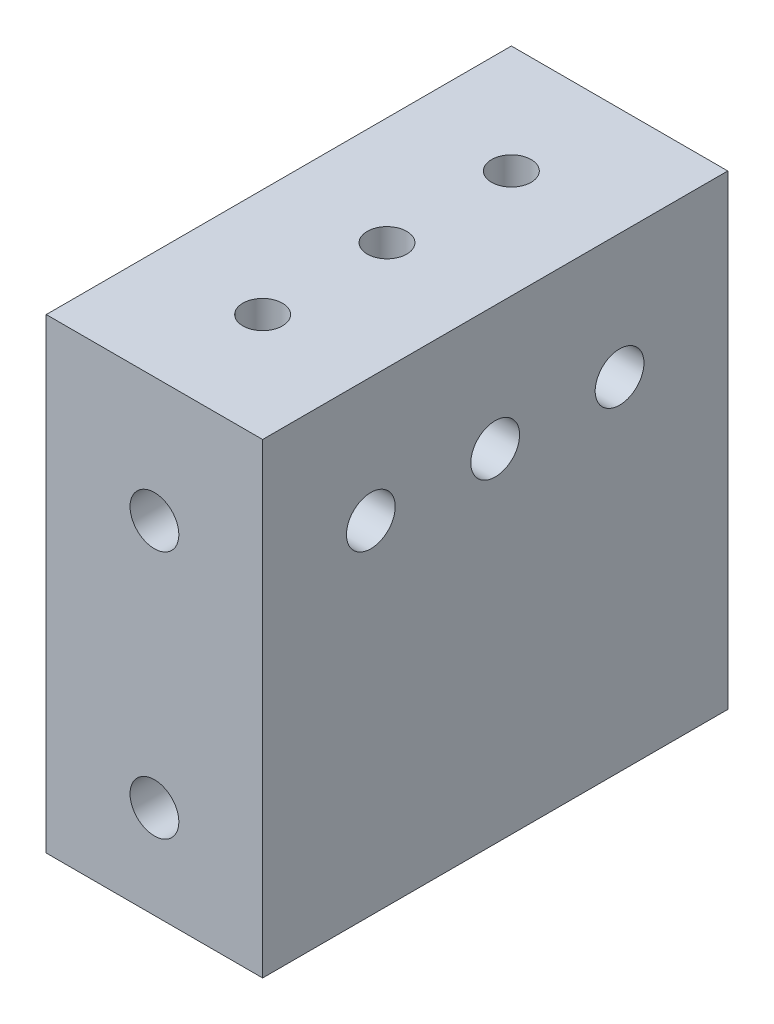
SolidWorks part; units mm, degrees
other "Markup1"
sketch "Sketch3" plane through (12.6365, 38.1, -23.749) normal (0.9027, 0.4189, -0.0984) x (-0.0151, -0.1977, -0.9801)
sketch "Sketch7" plane through (11.049, 23.8125, -23.749) normal (0.9027, 0.4189, -0.0984) x (-0.0151, -0.1977, -0.9801)
other "Markup2"
sketch "Sketch4" plane through (12.6365, 38.1, -23.749) normal (0.9027, 0.4189, -0.0984) x (-0.0151, -0.1977, -0.9801)
sketch "Sketch8" plane through (11.049, 23.8125, -23.749) normal (0.9027, 0.4189, -0.0984) x (-0.0151, -0.1977, -0.9801)
material "6061-T6 (SS)"
ref_plane "Front Plane" through (0, 0, 0) normal (0, 0, 1) x (1, 0, 0)
ref_plane "Top Plane" through (0, 0, 0) normal (0, 1, 0) x (1, 0, 0)
ref_plane "Right Plane" through (0, 0, 0) normal (1, 0, 0) x (0, 0, -1)
sketch "Sketch1" plane through (0, 0, 0) normal (0, 1, 0) x (1, 0, 0)
  line L0 (-12.6365, 25.3365) -> (12.6365, 25.3365)
  line L1 (-11.049, -23.749) -> (11.049, -23.749)
  line L2 (-11.049, -23.749) -> (-11.049, 23.749)
  line L3 (-11.049, 23.749) -> (11.049, 23.749)
  line L4 (11.049, -23.749) -> (11.049, 23.749)
  line L5 (-11.049, -23.749) -> (11.049, 23.749) construction
  line L6 (-11.049, 23.749) -> (11.049, -23.749) construction
  line L7 (12.6365, -25.3365) -> (12.6365, 25.3365)
  line L8 (-12.6365, -25.3365) -> (12.6365, -25.3365)
  line L9 (-12.6365, -25.3365) -> (-12.6365, 25.3365)
  point P0 (0, 0)
  dimension "D1" = 22.098
  dimension "D2" = 47.498
  dimension "D3" = 1.5875
extrude "Boss-Extrude1" add sketch "Sketch1" along normal mid plane 47.625 contours L1 L4 L3 L2 region at (0, 0, 0)
sketch "Sketch2" plane through (11.049, 0, 0) normal (1, 0, 0) x (0, 0, -1)
  line L0 (-23.749, 23.8125) -> (23.749, 23.8125) construction
  line L4 (-25.4, -23.8125) -> (25.4, -23.8125) construction
  line L5 (-25.4, -23.8125) -> (-25.4, 23.8125) construction
  line L6 (-25.4, 23.8125) -> (25.4, 23.8125) construction
  line L7 (25.4, -23.8125) -> (25.4, 23.8125) construction
  line L8 (-25.4, -23.8125) -> (25.4, 23.8125) construction
  line L9 (-25.4, 23.8125) -> (25.4, -23.8125) construction
  circle A0 centre (-12.7, 11.1125) radius 2.4892
  circle A1 centre (0, 11.1125) radius 2.4892
  circle A2 centre (12.7, 11.1125) radius 2.4892
  point P6 (0, 0)
  dimension "D1" = 4.9784
  dimension "D2" = 50.8
  dimension "D4" = 25.4
  dimension "D5" = 12.7
  dimension "D6" = 38.1
  dimension "D7" = 12.7
  dimension "D8" = 12.7
  dimension "D9" = 12.7
extrude "Cut-Extrude1" cut sketch "Sketch2" against normal blind 6.35
sketch "Sketch5" plane through (0, 0, -23.749) normal (0, 0, -1) x (-1, 0, 0)
  line L0 (11.049, 23.8125) -> (-11.049, 23.8125) construction
  line L1 (-12.7, -23.8125) -> (12.7, -23.8125) construction
  line L2 (-12.7, -23.8125) -> (-12.7, 23.8125) construction
  line L3 (-12.7, 23.8125) -> (12.7, 23.8125) construction
  line L4 (12.7, -23.8125) -> (12.7, 23.8125) construction
  line L5 (-12.7, -23.8125) -> (12.7, 23.8125) construction
  line L6 (-12.7, 23.8125) -> (12.7, -23.8125) construction
  circle A0 centre (0, 11.1125) radius 2.4892
  circle A2 centre (0, -14.2875) radius 2.4892
  point P0 (0, 0)
  dimension "D5" = 38.1
  dimension "D7" = 4.9784
  dimension "D8" = 4.9784
  dimension "D1" = 25.4
  dimension "D3" = 12.7
  dimension "D4" = 12.7
  dimension "D6" = 12.7
extrude "Cut-Extrude2" cut sketch "Sketch5" against normal through all
sketch "Sketch6" plane through (0, 23.8125, 0) normal (0, 1, 0) x (1, 0, 0)
  line L1 (11.049, -23.749) -> (11.049, 23.749) construction
  circle A0 centre (0, 0) radius 2.0193
  circle A1 centre (0, 12.7) radius 2.0193
  circle A2 centre (0, -12.7) radius 2.0193
  dimension "D3" = 4.0386
  dimension "D1" = 12.7
  dimension "D2" = 12.7
  dimension "D4" = 11.049
  dimension "D5" = 11.049
extrude "Cut-Extrude3" cut sketch "Sketch6" against normal blind 6.35
